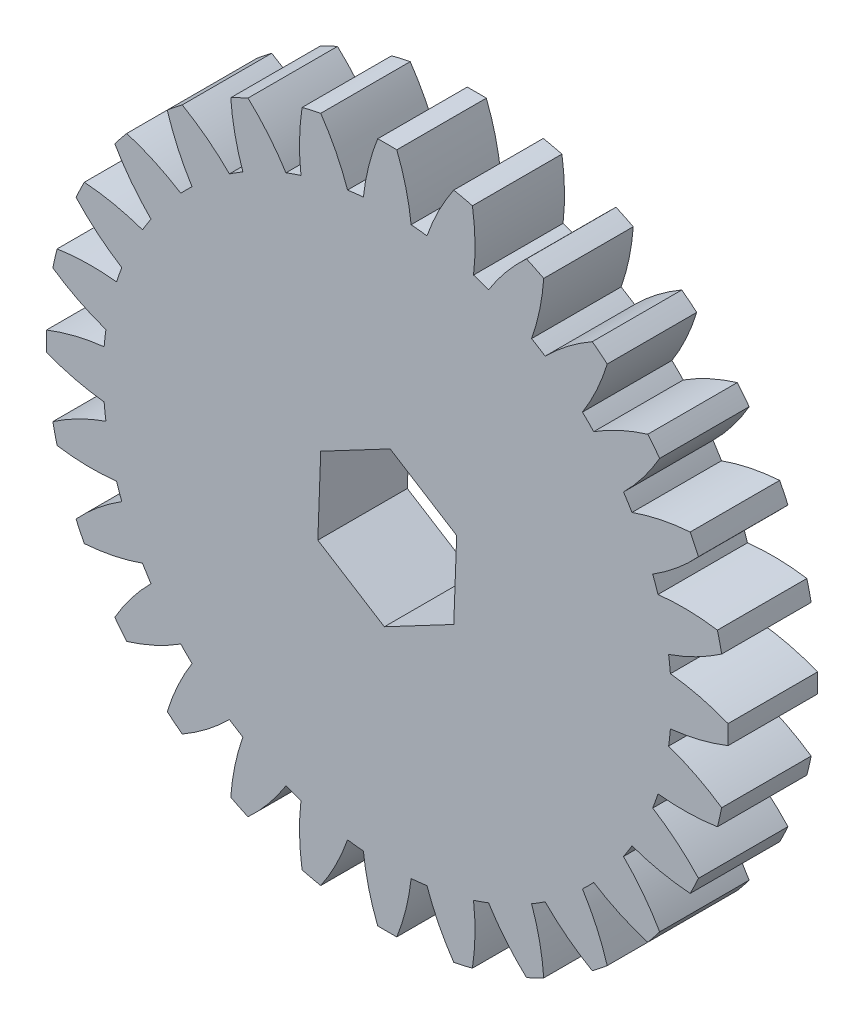
SolidWorks part; units mm, degrees
ref_plane "Front Plane" through (0, 0, 0) normal (0, 0, 1) x (1, 0, 0)
ref_plane "Top Plane" through (0, 0, 0) normal (0, 1, 0) x (1, 0, 0)
ref_plane "Right Plane" through (0, 0, 0) normal (1, 0, 0) x (0, 0, -1)
ref_plane "Plane1" through (0, 0, 5) normal (0, 0, 1) x (1, 0, 0)
sketch "Sketch1" plane through (0, 0, 5) normal (0, 0, 1) x (1, 0, 0)
  line L1 (-3.7162, 2.3331) -> (-3.8786, -2.0517)
  line L2 (-3.8786, -2.0517) -> (-0.1625, -4.3849)
  line L3 (0, 0) -> (-1.7774, 15.7752) construction
  line L4 (-0.1625, -4.3849) -> (3.7162, -2.3331)
  line L5 (3.7162, -2.3331) -> (3.8786, 2.0517)
  line L6 (3.8786, 2.0517) -> (0.1625, 4.3849)
  line L7 (0.1625, 4.3849) -> (-3.7162, 2.3331)
  arc A0 (-4.8209, 15.1253) -> (-5.6614, 14.8312) centre (0, 0) ccw
  arc A1 (-5.6614, 14.8312) -> (-7.7809, 17.3885) centre (-16.2618, 8.2026) ccw
  arc A2 (-7.7809, 17.3885) -> (-8.7436, 16.9249) centre (0, 0) ccw
  arc A3 (-8.7436, 16.9249) -> (-8.0657, 13.6733) centre (3.7261, 17.8282) ccw
  arc A4 (-8.0657, 13.6733) -> (-8.8197, 13.1996) centre (0, 0) ccw
  arc A5 (-8.8197, 13.1996) -> (-11.4551, 15.2211) centre (-17.6794, 4.3783) ccw
  arc A6 (-11.4551, 15.2211) -> (-12.2905, 14.5549) centre (0, 0) ccw
  arc A7 (-12.2905, 14.5549) -> (-10.9061, 11.5357) centre (-0.3345, 18.2104) ccw
  arc A8 (-10.9061, 11.5357) -> (-11.5357, 10.9061) centre (0, 0) ccw
  arc A9 (-11.5357, 10.9061) -> (-14.5549, 12.2905) centre (-18.2104, 0.3345) ccw
  arc A10 (-14.5549, 12.2905) -> (-15.2211, 11.4551) centre (0, 0) ccw
  arc A11 (-15.2211, 11.4551) -> (-13.1996, 8.8197) centre (-4.3783, 17.6794) ccw
  arc A12 (-13.1996, 8.8197) -> (-13.6733, 8.0657) centre (0, 0) ccw
  arc A13 (-13.6733, 8.0657) -> (-16.9249, 8.7436) centre (-17.8282, -3.7261) ccw
  arc A14 (-16.9249, 8.7436) -> (-17.3885, 7.7809) centre (0, 0) ccw
  arc A15 (-17.3885, 7.7809) -> (-14.8312, 5.6614) centre (-8.2026, 16.2618) ccw
  arc A16 (-14.8312, 5.6614) -> (-15.1253, 4.8209) centre (0, 0) ccw
  arc A17 (-15.1253, 4.8209) -> (-18.4462, 4.7582) centre (-16.5521, -7.5998) ccw
  arc A18 (-18.4462, 4.7582) -> (-18.684, 3.7165) centre (0, 0) ccw
  arc A19 (-18.684, 3.7165) -> (-15.7191, 2.2192) centre (-11.6155, 14.0289) ccw
  arc A20 (-15.7191, 2.2192) -> (-15.8188, 1.3343) centre (0, 0) ccw
  arc A21 (-15.8188, 1.3343) -> (-19.0425, 0.5343) centre (-14.446, -11.0924) ccw
  arc A22 (-19.0425, 0.5343) -> (-19.0425, -0.5343) centre (0, 0) ccw
  arc A23 (-19.0425, -0.5343) -> (-15.8188, -1.3343) centre (-14.446, 11.0924) ccw
  arc A24 (-15.8188, -1.3343) -> (-15.7191, -2.2192) centre (0, 0) ccw
  arc A25 (-15.7191, -2.2192) -> (-18.684, -3.7165) centre (-11.6155, -14.0289) ccw
  arc A26 (-18.684, -3.7165) -> (-18.4462, -4.7582) centre (0, 0) ccw
  arc A27 (-18.4462, -4.7582) -> (-15.1253, -4.8209) centre (-16.5521, 7.5998) ccw
  arc A28 (-15.1253, -4.8209) -> (-14.8312, -5.6614) centre (0, 0) ccw
  arc A29 (-14.8312, -5.6614) -> (-17.3885, -7.7809) centre (-8.2026, -16.2618) ccw
  arc A30 (-17.3885, -7.7809) -> (-16.9249, -8.7436) centre (0, 0) ccw
  arc A31 (-16.9249, -8.7436) -> (-13.6733, -8.0657) centre (-17.8282, 3.7261) ccw
  arc A32 (-13.6733, -8.0657) -> (-13.1996, -8.8197) centre (0, 0) ccw
  arc A33 (-13.1996, -8.8197) -> (-15.2211, -11.4551) centre (-4.3783, -17.6794) ccw
  arc A34 (-15.2211, -11.4551) -> (-14.5549, -12.2905) centre (0, 0) ccw
  arc A35 (-14.5549, -12.2905) -> (-11.5357, -10.9061) centre (-18.2104, -0.3345) ccw
  arc A36 (-11.5357, -10.9061) -> (-10.9061, -11.5357) centre (0, 0) ccw
  arc A37 (-10.9061, -11.5357) -> (-12.2905, -14.5549) centre (-0.3345, -18.2104) ccw
  arc A38 (-12.2905, -14.5549) -> (-11.4551, -15.2211) centre (0, 0) ccw
  arc A39 (-11.4551, -15.2211) -> (-8.8197, -13.1996) centre (-17.6794, -4.3783) ccw
  arc A40 (-8.8197, -13.1996) -> (-8.0657, -13.6733) centre (0, 0) ccw
  arc A41 (-8.0657, -13.6733) -> (-8.7436, -16.9249) centre (3.7261, -17.8282) ccw
  arc A42 (-8.7436, -16.9249) -> (-7.7809, -17.3885) centre (0, 0) ccw
  arc A43 (-7.7809, -17.3885) -> (-5.6614, -14.8312) centre (-16.2618, -8.2026) ccw
  arc A44 (-5.6614, -14.8312) -> (-4.8209, -15.1253) centre (0, 0) ccw
  arc A45 (-4.8209, -15.1253) -> (-4.7582, -18.4462) centre (7.5998, -16.5521) ccw
  arc A46 (-4.7582, -18.4462) -> (-3.7165, -18.684) centre (0, 0) ccw
  arc A47 (-3.7165, -18.684) -> (-2.2192, -15.7191) centre (-14.0289, -11.6155) ccw
  arc A48 (-2.2192, -15.7191) -> (-1.3343, -15.8188) centre (0, 0) ccw
  arc A49 (-1.3343, -15.8188) -> (-0.5343, -19.0425) centre (11.0924, -14.446) ccw
  arc A50 (-0.5343, -19.0425) -> (0.5343, -19.0425) centre (0, 0) ccw
  arc A51 (0.5343, -19.0425) -> (1.3343, -15.8188) centre (-11.0924, -14.446) ccw
  arc A52 (1.3343, -15.8188) -> (2.2192, -15.7191) centre (0, 0) ccw
  arc A53 (2.2192, -15.7191) -> (3.7165, -18.684) centre (14.0289, -11.6155) ccw
  arc A54 (3.7165, -18.684) -> (4.7582, -18.4462) centre (0, 0) ccw
  arc A55 (4.7582, -18.4462) -> (4.8209, -15.1253) centre (-7.5998, -16.5521) ccw
  arc A56 (4.8209, -15.1253) -> (5.6614, -14.8312) centre (0, 0) ccw
  arc A57 (5.6614, -14.8312) -> (7.7809, -17.3885) centre (16.2618, -8.2026) ccw
  arc A58 (7.7809, -17.3885) -> (8.7436, -16.9249) centre (0, 0) ccw
  arc A59 (8.7436, -16.9249) -> (8.0657, -13.6733) centre (-3.7261, -17.8282) ccw
  arc A60 (8.0657, -13.6733) -> (8.8197, -13.1996) centre (0, 0) ccw
  arc A61 (8.8197, -13.1996) -> (11.4551, -15.2211) centre (17.6794, -4.3783) ccw
  arc A62 (11.4551, -15.2211) -> (12.2905, -14.5549) centre (0, 0) ccw
  arc A63 (12.2905, -14.5549) -> (10.9061, -11.5357) centre (0.3345, -18.2104) ccw
  arc A64 (10.9061, -11.5357) -> (11.5357, -10.9061) centre (0, 0) ccw
  arc A65 (11.5357, -10.9061) -> (14.5549, -12.2905) centre (18.2104, -0.3345) ccw
  arc A66 (14.5549, -12.2905) -> (15.2211, -11.4551) centre (0, 0) ccw
  arc A67 (15.2211, -11.4551) -> (13.1996, -8.8197) centre (4.3783, -17.6794) ccw
  arc A68 (13.1996, -8.8197) -> (13.6733, -8.0657) centre (0, 0) ccw
  arc A69 (13.6733, -8.0657) -> (16.9249, -8.7436) centre (17.8282, 3.7261) ccw
  arc A70 (16.9249, -8.7436) -> (17.3885, -7.7809) centre (0, 0) ccw
  arc A71 (17.3885, -7.7809) -> (14.8312, -5.6614) centre (8.2026, -16.2618) ccw
  arc A72 (14.8312, -5.6614) -> (15.1253, -4.8209) centre (0, 0) ccw
  arc A73 (15.1253, -4.8209) -> (18.4462, -4.7582) centre (16.5521, 7.5998) ccw
  arc A74 (18.4462, -4.7582) -> (18.684, -3.7165) centre (0, 0) ccw
  arc A75 (18.684, -3.7165) -> (15.7191, -2.2192) centre (11.6155, -14.0289) ccw
  arc A76 (15.7191, -2.2192) -> (15.8188, -1.3343) centre (0, 0) ccw
  arc A77 (15.8188, -1.3343) -> (19.0425, -0.5343) centre (14.446, 11.0924) ccw
  arc A78 (19.0425, -0.5343) -> (19.0425, 0.5343) centre (0, 0) ccw
  arc A79 (19.0425, 0.5343) -> (15.8188, 1.3343) centre (14.446, -11.0924) ccw
  arc A80 (15.8188, 1.3343) -> (15.7191, 2.2192) centre (0, 0) ccw
  arc A81 (15.7191, 2.2192) -> (18.684, 3.7165) centre (11.6155, 14.0289) ccw
  arc A82 (18.684, 3.7165) -> (18.4462, 4.7582) centre (0, 0) ccw
  arc A83 (18.4462, 4.7582) -> (15.1253, 4.8209) centre (16.5521, -7.5998) ccw
  arc A84 (15.1253, 4.8209) -> (14.8312, 5.6614) centre (0, 0) ccw
  arc A85 (14.8312, 5.6614) -> (17.3885, 7.7809) centre (8.2026, 16.2618) ccw
  arc A86 (17.3885, 7.7809) -> (16.9249, 8.7436) centre (0, 0) ccw
  arc A87 (16.9249, 8.7436) -> (13.6733, 8.0657) centre (17.8282, -3.7261) ccw
  arc A88 (13.6733, 8.0657) -> (13.1996, 8.8197) centre (0, 0) ccw
  arc A89 (13.1996, 8.8197) -> (15.2211, 11.4551) centre (4.3783, 17.6794) ccw
  arc A90 (15.2211, 11.4551) -> (14.5549, 12.2905) centre (0, 0) ccw
  arc A91 (14.5549, 12.2905) -> (11.5357, 10.9061) centre (18.2104, 0.3345) ccw
  arc A92 (11.5357, 10.9061) -> (10.9061, 11.5357) centre (0, 0) ccw
  arc A93 (10.9061, 11.5357) -> (12.2905, 14.5549) centre (0.3345, 18.2104) ccw
  arc A94 (12.2905, 14.5549) -> (11.4551, 15.2211) centre (0, 0) ccw
  arc A95 (11.4551, 15.2211) -> (8.8197, 13.1996) centre (17.6794, 4.3783) ccw
  arc A96 (8.8197, 13.1996) -> (8.0657, 13.6733) centre (0, 0) ccw
  arc A97 (8.0657, 13.6733) -> (8.7436, 16.9249) centre (-3.7261, 17.8282) ccw
  arc A98 (8.7436, 16.9249) -> (7.7809, 17.3885) centre (0, 0) ccw
  arc A99 (7.7809, 17.3885) -> (5.6614, 14.8312) centre (16.2618, 8.2026) ccw
  arc A100 (5.6614, 14.8312) -> (4.8209, 15.1253) centre (0, 0) ccw
  arc A101 (4.8209, 15.1253) -> (4.7582, 18.4462) centre (-7.5998, 16.5521) ccw
  arc A102 (4.7582, 18.4462) -> (3.7165, 18.684) centre (0, 0) ccw
  arc A103 (3.7165, 18.684) -> (2.2192, 15.7191) centre (14.0289, 11.6155) ccw
  arc A104 (2.2192, 15.7191) -> (1.3343, 15.8188) centre (0, 0) ccw
  arc A105 (1.3343, 15.8188) -> (0.5343, 19.0425) centre (-11.0924, 14.446) ccw
  arc A106 (0.5343, 19.0425) -> (-0.5343, 19.0425) centre (0, 0) ccw
  arc A107 (-0.5343, 19.0425) -> (-1.3343, 15.8188) centre (11.0924, 14.446) ccw
  arc A108 (-1.3343, 15.8188) -> (-2.2192, 15.7191) centre (0, 0) ccw
  arc A109 (-2.2192, 15.7191) -> (-3.7165, 18.684) centre (-14.0289, 11.6155) ccw
  arc A110 (-3.7165, 18.684) -> (-4.7582, 18.4462) centre (0, 0) ccw
  arc A111 (-4.7582, 18.4462) -> (-4.8209, 15.1253) centre (7.5998, 16.5521) ccw
  circle A112 centre (0, 0) radius 3.8 construction
  dimension "D2" = 7.6
  dimension "D1" = 19.05
extrude "Boss-Extrude1" add sketch "Sketch1" against normal blind 5
ref_axis "Axis1" through (0, 0, -0.25) along (0, 0, 1)
sketch "Sketch3" [suppressed] plane through (0, 0, 5) normal (0, 0, 1) x (1, 0, 0)
  line L0 (0, 0) -> (4.239, 18.5724) construction
  line L1 (11.2253, 11.2253) -> (0, 0) construction
  line L2 (8.446, -13.4417) -> (0, 0) construction
  arc A0 (4.7582, 18.4462) -> (3.7165, 18.684) centre (0, 0) ccw construction
  arc A1 (11.5357, 10.9061) -> (10.9061, 11.5357) centre (0, 0) ccw construction
  arc A3 (8.0657, -13.6733) -> (8.8197, -13.1996) centre (0, 0) ccw construction
